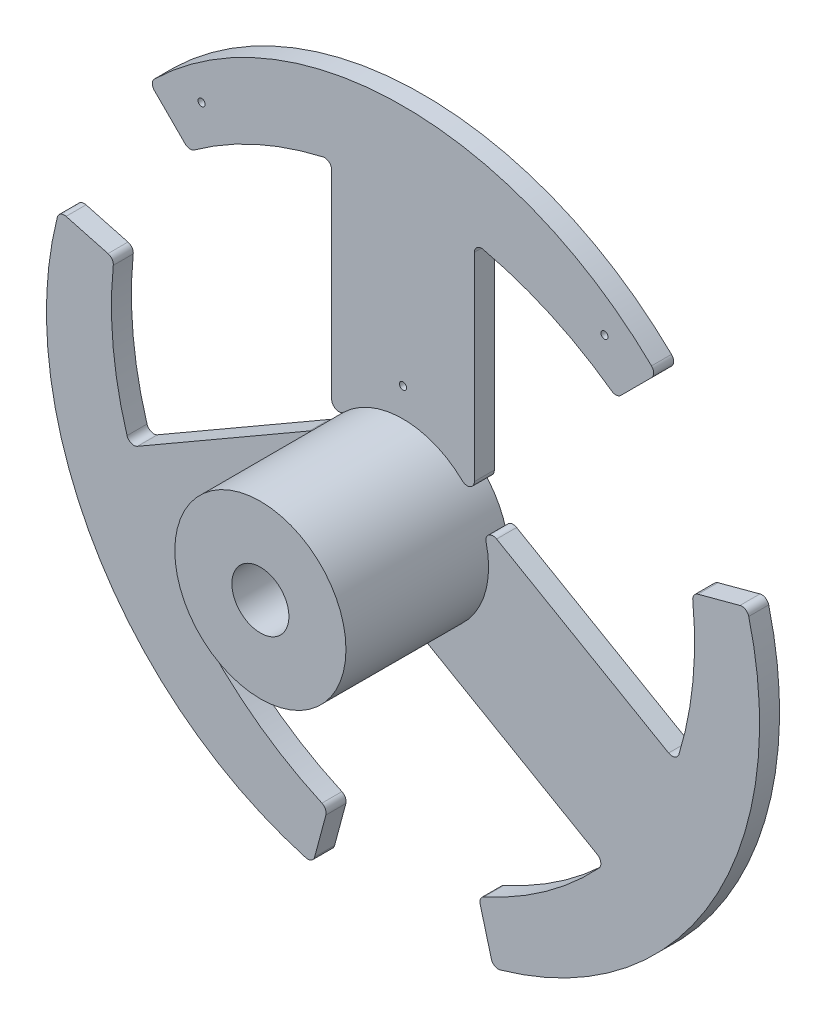
SolidWorks part; units mm, degrees
ref_plane "Front Plane" through (0, 0, 0) normal (0, 0, 1) x (1, 0, 0)
ref_plane "Top Plane" through (0, 0, 0) normal (0, 1, 0) x (1, 0, 0)
ref_plane "Right Plane" through (0, 0, 0) normal (1, 0, 0) x (0, 0, -1)
sketch "Sketch1" plane through (0, 0, 0) normal (0, 0, 1) x (1, 0, 0)
  line L0 (-39.7176, 82.9924) -> (-39.7176, 177.9924) construction
  line L1 (28.3744, -15.1934) -> (-31.9137, 19.6139)
  line L2 (-14.713, 146.0547) -> (-14.713, 76.44)
  line L3 (-64.7223, 146.0547) -> (-64.7223, 76.44)
  line L4 (-114.3623, 126.7922) -> (-114.571, 126.7922)
  line L5 (-127.5882, 140.863) -> (-60.99, 74.2648) construction
  line L6 (-18.4452, 74.2648) -> (48.153, 140.863) construction
  line L7 (36.6534, 128.31) -> (47.4208, 139.0774)
  line L8 (53.379, 28.1159) -> (-6.9091, 62.9233)
  line L9 (63.6948, 81.4729) -> (78.4033, 85.4141)
  line L10 (-116.0887, 128.31) -> (-126.8561, 139.0774)
  line L11 (-12.6762, -50.8057) -> (-8.7351, -65.5142)
  line L12 (-132.8143, 28.1159) -> (-72.5262, 62.9233)
  line L13 (-107.8096, -15.1934) -> (-47.5215, 19.6139)
  line L14 (-66.759, -50.8057) -> (-70.7002, -65.5142)
  line L15 (-143.1301, 81.4729) -> (-157.8386, 85.4141)
  arc A0 (33.4229, 128.0504) -> (-11.6517, 148.4909) centre (-39.7176, 26.6824) ccw
  arc A1 (47.3953, 142.638) -> (-126.8306, 142.638) centre (-39.7176, 52.9924) ccw
  arc A2 (-18.9441, 74.6364) -> (-60.4912, 74.6364) centre (-39.7176, 52.9924) ccw
  arc A3 (-14.713, 76.44) -> (-18.9441, 74.6364) centre (-17.213, 76.44) cw
  arc A4 (-64.7223, 76.44) -> (-60.4912, 74.6364) centre (-62.2223, 76.44) ccw
  arc A5 (-67.7836, 148.4909) -> (-112.8581, 128.0504) centre (-39.7176, 26.6824) ccw
  arc A6 (36.6534, 128.31) -> (33.4229, 128.0504) centre (34.8857, 130.0778) cw
  arc A7 (47.4208, 139.0774) -> (47.3953, 142.638) centre (45.653, 140.8451) ccw
  arc A8 (-126.8561, 139.0774) -> (-126.8306, 142.638) centre (-125.0883, 140.8451) cw
  arc A9 (-116.0887, 128.31) -> (-112.8581, 128.0504) centre (-114.3209, 130.0778) ccw
  arc A10 (-11.6517, 148.4909) -> (-14.713, 146.0547) centre (-12.213, 146.0547) ccw
  arc A11 (-64.7223, 146.0547) -> (-67.7836, 148.4909) centre (-67.2223, 146.0547) ccw
  circle A13 centre (-110.3279, 143.7624) radius 1.25
  circle A14 centre (30.8926, 143.7624) radius 1.25
  circle A15 centre (-39.7176, 92.9924) radius 1.25
  arc A16 (28.9535, -19.0627) -> (28.3744, -15.1934) centre (27.1244, -17.3585) ccw
  arc A17 (-31.9137, 19.6139) -> (-31.3602, 24.18) centre (-30.6637, 21.779) cw
  arc A18 (-31.3602, 24.18) -> (-10.5867, 60.1608) centre (-39.7176, 52.9924) ccw
  arc A19 (-6.9091, 62.9233) -> (-10.5867, 60.1608) centre (-8.1591, 60.7582) ccw
  arc A20 (53.379, 28.1159) -> (57.0194, 29.549) centre (54.629, 30.281) ccw
  arc A21 (57.0194, 29.549) -> (61.8547, 78.805) centre (-62.5028, 66.1474) ccw
  arc A22 (63.6948, 81.4729) -> (61.8547, 78.805) centre (64.3419, 79.0581) ccw
  arc A23 (78.4033, 85.4141) -> (81.4742, 83.6116) centre (79.0504, 82.9992) cw
  arc A24 (-5.6387, -67.2724) -> (81.4742, 83.6116) centre (-39.7176, 52.9924) ccw
  arc A25 (-8.7351, -65.5142) -> (-5.6387, -67.2724) centre (-6.3203, -64.8671) ccw
  arc A26 (-12.6762, -50.8057) -> (-11.2858, -47.8781) centre (-10.2614, -50.1586) cw
  arc A27 (-11.2858, -47.8781) -> (28.9535, -19.0627) centre (-62.5028, 66.1474) ccw
  arc A28 (-136.4547, 29.549) -> (-132.8143, 28.1159) centre (-134.0643, 30.281) ccw
  arc A29 (-72.5262, 62.9233) -> (-68.8486, 60.1608) centre (-71.2762, 60.7582) cw
  arc A30 (-68.8486, 60.1608) -> (-48.0751, 24.18) centre (-39.7176, 52.9924) ccw
  arc A31 (-47.5215, 19.6139) -> (-48.0751, 24.18) centre (-48.7715, 21.779) ccw
  arc A32 (-107.8096, -15.1934) -> (-108.3887, -19.0627) centre (-106.5596, -17.3585) ccw
  arc A33 (-108.3887, -19.0627) -> (-68.1495, -47.8781) centre (-16.9325, 66.1474) ccw
  arc A34 (-66.759, -50.8057) -> (-68.1495, -47.8781) centre (-69.1738, -50.1586) ccw
  arc A35 (-70.7002, -65.5142) -> (-73.7965, -67.2724) centre (-73.115, -64.8671) cw
  arc A36 (-160.9095, 83.6116) -> (-73.7965, -67.2724) centre (-39.7176, 52.9924) ccw
  arc A37 (-157.8386, 85.4141) -> (-160.9095, 83.6116) centre (-158.4856, 82.9992) ccw
  arc A38 (-143.1301, 81.4729) -> (-141.29, 78.805) centre (-143.7771, 79.0581) cw
  arc A39 (-141.29, 78.805) -> (-136.4547, 29.549) centre (-16.9325, 66.1474) ccw
  circle A40 centre (-39.7176, 52.9924) radius 30
  circle A41 centre (-39.7176, 52.9924) radius 10
  point P9 (-42.8309, 76.2572)
  point P18 (-39.7176, 132.0448)
  point P21 (-114.571, 126.7922)
  point P46 (-63.2026, 74.1403)
  point P51 (-16.2326, 74.1403)
  point P56 (-39.7176, 82.9924)
  point P99 (-39.7176, 52.9924)
  dimension "D1" = 125
  dimension "D2" = 125
  dimension "D4" = 15
  dimension "D7" = 2.5
  dimension "D10" = 2.5
  dimension "D5" = 3
  dimension "D12" = 2.5
  dimension "D15" = 45
  dimension "D9" = 2.5
  dimension "D6" = 20
  dimension "D3" = 10
  dimension "D16" = 46.97
extrude "Boss-Extrude1" add sketch "Sketch1" along normal blind 7 contours A11 L3 A4 A2 A3 L2 A10 A0 A6 L7 A7 A1 A8 L10 A9 A5 A15 A13 A14 region at (-39.7176, 137.174, 0)
extrude "Boss-Extrude2" add sketch "Sketch1<5>" along normal blind 7 separate body contours A39 A38 L15 A37 A36 A35 L14 A34 A33 A32 L13 A31 A30 A29 L12 A28 | A27 A26 L11 A25 A24 A23 L9 A22 A21 A20 L8 A19 A18 A17 L1 A16 region at (33.1691, 10.9113, 0) region at (-112.6043, 10.9113, 0)
sketch "Sketch1<5>" plane through (0, 0, 0) normal (0, 0, 1) x (1, 0, 0) same geometry as "Sketch1"
extrude "Boss-Extrude3" add sketch "Sketch1<7>" along normal blind 57 contours A18 A40 A2 A30 region at (-39.7176, 23.8409, 0)
sketch "Sketch1<7>" plane through (0, 0, 0) normal (0, 0, 1) x (1, 0, 0) same geometry as "Sketch1"
